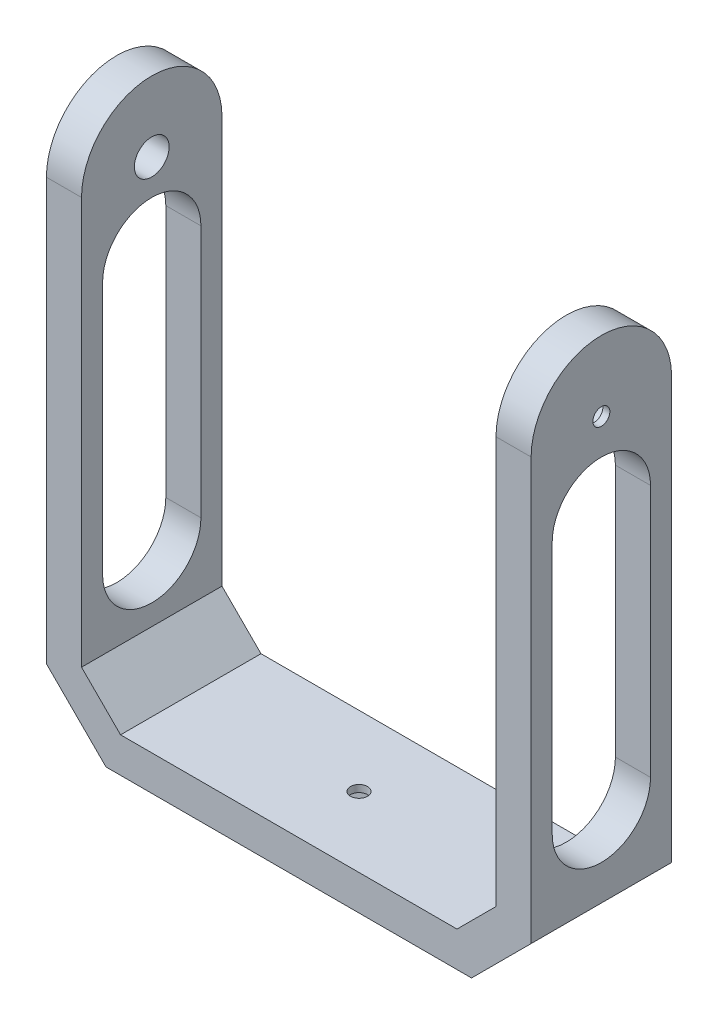
SolidWorks part; units mm, degrees
ref_plane "Front Plane" through (0, 0, 0) normal (0, 0, 1) x (1, 0, 0)
ref_plane "Top Plane" through (0, 0, 0) normal (0, 1, 0) x (1, 0, 0)
ref_plane "Right Plane" through (0, 0, 0) normal (1, 0, 0) x (0, 0, -1)
sketch "Sketch1" plane through (0, 0, 0) normal (0, 0, 1) x (1, 0, 0)
  line L12 (0, 2.5) -> (0, -2.5) construction
  line L13 (-26.0247, -2.5) -> (26.0247, -2.5)
  line L14 (26.0247, -2.5) -> (34.51, 5.9853)
  line L15 (34.51, 5.9853) -> (34.51, 75.9853)
  line L16 (34.51, 75.9853) -> (29.51, 75.9853)
  line L17 (29.51, 75.9853) -> (29.51, 8.0563)
  line L18 (29.51, 8.0563) -> (23.9537, 2.5)
  line L19 (23.9537, 2.5) -> (-23.9537, 2.5)
  line L20 (-29.51, 8.0563) -> (-23.9537, 2.5)
  line L21 (-29.51, 75.9853) -> (-29.51, 8.0563)
  line L22 (-34.51, 75.9853) -> (-29.51, 75.9853)
  line L23 (-34.51, 5.9853) -> (-34.51, 75.9853)
  line L24 (-26.0247, -2.5) -> (-34.51, 5.9853)
  point P0 (0, 0)
  dimension "D1" = 5
  dimension "D2" = 59.02
  dimension "D3" = 5
  dimension "D4" = 45
  dimension "D5" = 70
  dimension "D6" = 12
extrude "Boss-Extrude1" add sketch "Sketch1" along normal blind 20
fillet "Fillet2" 2 edges at (-32.01, 75.9853, 20) (-32.01, 75.9853, 0) type full round first side face at (0, 27.6687, 20) second side face at (0, 27.6687, 0) middle face at (-32.01, 75.9853, 10)
fillet "Fillet3" 2 edges at (32.01, 75.9853, 20) (32.01, 75.9853, 0) type full round first side face at (0, 26.002, 20) second side face at (0, 26.002, 0) middle face at (32.01, 75.9853, 10)
sketch "Sketch2" plane through (0, -2.5, 0) normal (0, -1, 0) x (1, 0, 0)
  line L0 (26.0247, 20) -> (26.0247, 0) construction
  line L1 (-18, 13.775) -> (18, 13.775)
  line L2 (-18, 13.775) -> (-18, 6.225)
  line L3 (-18, 6.225) -> (18, 6.225)
  line L4 (18, 13.775) -> (18, 6.225)
  line L5 (-18, 13.775) -> (18, 6.225) construction
  line L6 (-18, 6.225) -> (18, 13.775) construction
  point P0 (0, 10)
  point P7 (26.0247, 10)
  point P10 (18, 10)
  dimension "D1" = 7.55
  dimension "D2" = 36
extrude "Cut-Extrude1" cut sketch "Sketch2" against normal blind 3
ref_plane "Plane1" through (0, -12.5, 0) normal (0, -1, 0) x (-1, 0, 0)
sketch "Sketch3" plane through (0, -12.5, 0) normal (0, -1, 0) x (-1, 0, 0)
  circle A0 centre (0, -12.4243) radius 30.5442
  dimension "D1" = 61.0884
extrude "Boss-Extrude2" [suppressed] add sketch "Sketch3" against normal blind 10 draft 24 and the other way blind 10
sketch "Sketch4" plane through (0, 0.5, 0) normal (0, -1, 0) x (1, 0, 0)
  line L0 (18, 6.225) -> (18, 13.775) construction
  circle A0 centre (0, 10) radius 1.21
  point P5 (18, 10)
  dimension "D1" = 2.42
extrude "Cut-Extrude2" cut sketch "Sketch4" against normal up to next
sketch "Sketch6" plane through (0, 0.5, 0) normal (0, -1, 0) x (1, 0, 0)
  line L0 (18, 13.775) -> (-18, 13.775) construction
  line L1 (-5, 13.775) -> (5, 13.775)
  line L2 (-5, 13.775) -> (-5, 6.225)
  line L3 (-5, 6.225) -> (5, 6.225)
  line L4 (5, 13.775) -> (5, 6.225)
  line L5 (-5, 13.775) -> (5, 6.225) construction
  line L6 (-5, 6.225) -> (5, 13.775) construction
  point P0 (0, 10)
  dimension "D2" = 10
extrude "Cut-Extrude3" cut sketch "Sketch6" against normal blind 1
sketch "Sketch7" plane through (29.51, 0, 0) normal (-1, 0, 0) x (0, 0, 1)
  line L0 (20, 8.0563) -> (0, 8.0563) construction
  circle A0 centre (10, 65.9853) radius 2.45
  arc A1 (20, 65.9853) -> (0, 65.9853) centre (10, 65.9853) ccw construction
  point P5 (10, 8.0563)
  point P9 (10, 75.9853)
  dimension "D1" = 4.9
  dimension "D2" = 10
extrude "Cut-Extrude4" cut sketch "Sketch7" against normal offset from surface (4 mm away) 1 up to face at (34.51, 38.4853, 10)
sketch "Sketch9" plane through (33.51, 0, 0) normal (-1, 0, 0) x (0, 0, 1)
  circle A0 centre (10, 65.9853) radius 1.21
  dimension "D1" = 2.42
extrude "Cut-Extrude5" cut sketch "Sketch9" against normal up to next
sketch "Sketch10" plane through (-29.51, 0, 0) normal (1, 0, 0) x (0, 0, -1)
  line L0 (-20, 8.0563) -> (0, 8.0563) construction
  circle A0 centre (-10, 65.9853) radius 2.475
  arc A1 (0, 65.9853) -> (-20, 65.9853) centre (-10, 65.9853) ccw construction
  point P5 (-10, 8.0563)
  point P9 (-10, 75.9853)
  dimension "D1" = 4.95
  dimension "D2" = 10
extrude "Cut-Extrude6" cut sketch "Sketch10" against normal offset from surface (4 mm away) 1 up to face at (-34.51, 38.4853, 10)
sketch "Sketch11" plane through (34.51, 0, 0) normal (1, 0, 0) x (0, 0, -1)
  line L0 (-10, 53.9853) -> (-10, 17.9853) construction
  line L1 (-3, 53.9853) -> (-3, 17.9853)
  line L2 (-17, 53.9853) -> (-17, 17.9853)
  line L3 (-20, 5.9853) -> (0, 5.9853) construction
  arc A0 (-3, 53.9853) -> (-17, 53.9853) centre (-10, 53.9853) ccw
  arc A1 (-17, 17.9853) -> (-3, 17.9853) centre (-10, 17.9853) ccw
  point P2 (-10, 35.9853)
  point P17 (-10, 5.9853)
  point P18 (-10, 10.9853)
  dimension "D2" = 7
  dimension "D1" = 36
  dimension "D3" = 5
extrude "Cut-Extrude7" cut sketch "Sketch11" against normal through all
